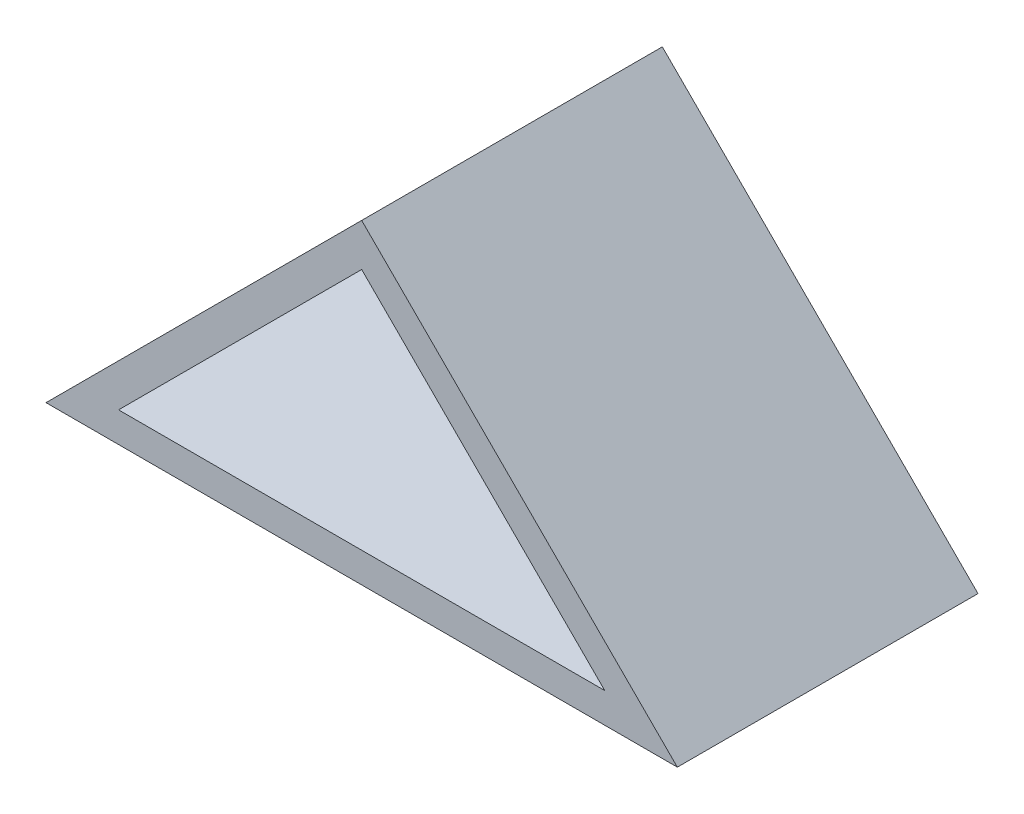
SolidWorks part; units mm, degrees
ref_plane "Front Plane" through (0, 0, 0) normal (0, 0, 1) x (1, 0, 0)
ref_plane "Top Plane" through (0, 0, 0) normal (0, 1, 0) x (1, 0, 0)
ref_plane "Right Plane" through (0, 0, 0) normal (1, 0, 0) x (0, 0, -1)
sketch "Sketch1" plane through (0, 0, 0) normal (0, 0, 1) x (1, 0, 0)
  line L1 (0, 0) -> (-42, -42)
  line L2 (0, -1000.3549) -> (0, 48999.6451) construction
  line L3 (-32.3431, -38) -> (0, -5.6569)
  line L4 (32.3431, -38) -> (0, -5.6569)
  line L5 (0, 0) -> (42, -42)
  line L7 (-42, -42) -> (42, -42)
  line L8 (-32.3431, -38) -> (32.3431, -38)
  line L9 (-34, -34) -> (34, -34) construction
  dimension "D1" = 90
  dimension "D2" = 4
  dimension "D3" = 4
  dimension "D4" = 68
  dimension "D5" = 8
extrude "Boss-Extrude1" add sketch "Sketch1" along normal mid plane 40
sketch "Sketch2" plane through (0, 0, 0) normal (1, 0, 0) x (0, 0, -1)
  line L0 (0, -1034.3624) -> (0, 48965.6376) construction
  line L1 (-20, -42) -> (20, -42) construction
  line L2 (-3.5, -42) -> (-3.5, -65.5)
  line L3 (-3.5, -65.5) -> (-9, -65.5)
  line L4 (-9, -65.5) -> (-9, -69)
  line L5 (-9, -69) -> (9, -69)
  line L6 (9, -65.5) -> (9, -69)
  line L7 (3.5, -65.5) -> (9, -65.5)
  line L8 (3.5, -42) -> (3.5, -65.5)
  line L9 (3.5, -42) -> (-3.5, -42)
  point P5 (0, -42)
  dimension "D1" = 7
  dimension "D2" = 3.5
  dimension "D3" = 27
  dimension "D4" = 18
extrude "Boss-Extrude2" [suppressed] add sketch "Sketch2" along normal blind 6 from vertex starting at point (-42, -42, 0)
sketch "Sketch4" [suppressed] plane through (0, 0, 0) normal (1, 0, 0) x (0, 0, -1)
  line L0 (-20, -38.4859) -> (20, -38.4859) construction
  line L1 (3.5, -38.4859) -> (13.5, -38.4859)
  line L2 (3.5, -38.4859) -> (3.5, -65.4859)
  line L3 (3.5, -65.4859) -> (13.5, -65.4859)
  line L4 (13.5, -38.4859) -> (13.5, -65.4859)
  line L5 (-9, -65.4859) -> (9, -65.4859) construction
  line L7 (-11, -38.4859) -> (-18.5, -38.4859)
  line L8 (-11, -38.4859) -> (-11, -65.4859)
  line L9 (-11, -65.4859) -> (-18.5, -65.4859)
  line L10 (-18.5, -38.4859) -> (-18.5, -65.4859)
  line L11 (-9, -61.9859) -> (-9, -65.4859) construction
  dimension "D1" = 10
  dimension "D2" = 2
  dimension "D3" = 7.5
extrude "Boss-Extrude3" [suppressed] add sketch "Sketch4" against normal blind 6 from vertex starting at point (42, -42, 20)
